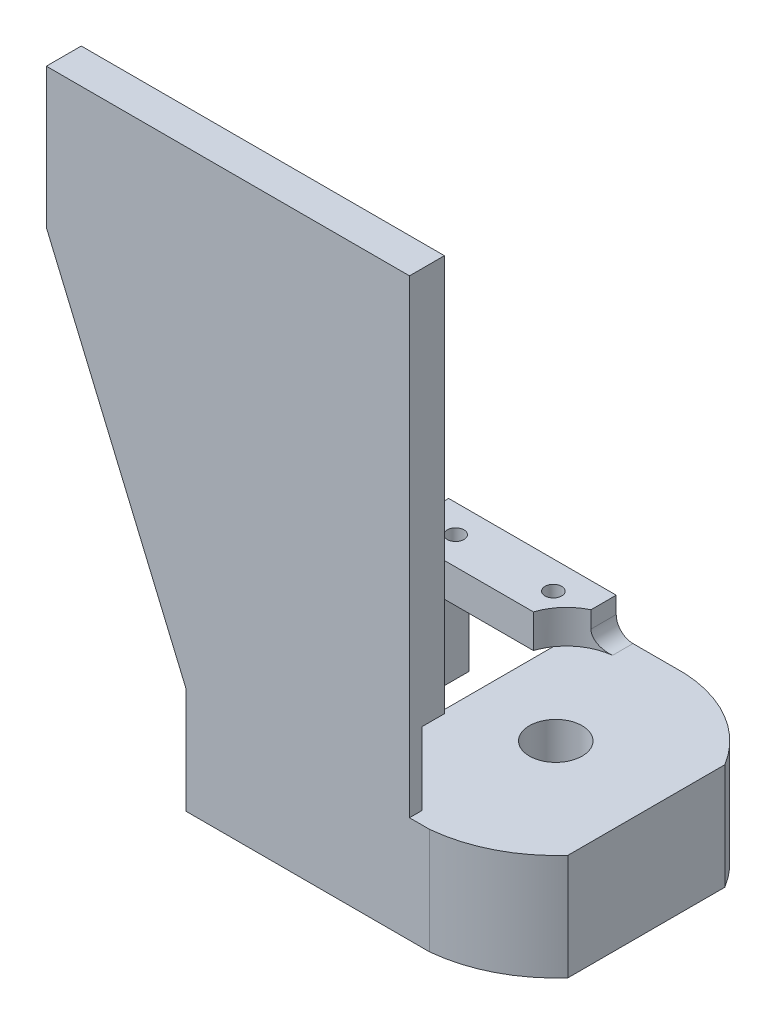
SolidWorks part; units mm, degrees
ref_plane "Front Plane" through (0, 0, 0) normal (0, 0, 1) x (1, 0, 0)
ref_plane "Top Plane" through (0, 0, 0) normal (0, 1, 0) x (1, 0, 0)
ref_plane "Right Plane" through (0, 0, 0) normal (1, 0, 0) x (0, 0, -1)
sketch "Sketch1" plane through (0, 0, 0) normal (0, 1, 0) x (1, 0, 0)
  line L0 (-5.7502, 0) -> (11.7498, 0) construction
  circle A0 centre (-5.7502, 0) radius 1.5 construction
  circle A1 centre (11.7498, 0) radius 1.5 construction
  dimension "D1" = 3
  dimension "D2" = 17.5
sketch "Sketch2" plane through (0, 0, 0) normal (0, 1, 0) x (1, 0, 0)
  line L0 (2.9998, -5) -> (2.9998, 5) construction
  line L1 (-12.0002, -5) -> (17.9998, -5)
  line L2 (-12.0002, -5) -> (-12.0002, 5)
  line L3 (-12.0002, 5) -> (17.9998, 5)
  line L4 (17.9998, -5) -> (17.9998, 5)
  line L5 (-5.7502, 0) -> (11.7498, 0) construction
  line L6 (-12.0002, 0) -> (17.9998, 0) construction
  point P6 (2.9998, 0)
  point P11 (2.9998, 0)
  dimension "D1" = 30
  dimension "D2" = 10
extrude "Boss-Extrude1" add sketch "Sketch2" along normal blind 25
sketch "Sketch3" plane through (0, 0, 5) normal (0, 0, 1) x (1, 0, 0)
  line L0 (2.9998, 25) -> (2.9998, 0) construction
  line L1 (-12.0002, 25) -> (17.9998, 25) construction
  line L2 (-5.7502, 0) -> (11.7498, 0) construction
  line L3 (-12.0002, 12.5) -> (17.9998, 12.5) construction
  line L4 (-12.0002, 25) -> (-12.0002, 0) construction
  line L5 (17.9998, 25) -> (17.9998, 0) construction
  line L6 (-12.0002, 0) -> (17.9998, 0) construction
  line L7 (-8.3502, 0) -> (14.3498, 0)
  line L8 (-8.3502, 0) -> (-8.3502, 19)
  line L9 (-8.3502, 19) -> (14.3498, 19)
  line L10 (14.3498, 0) -> (14.3498, 19)
  line L11 (-8.3502, 0) -> (14.3498, 19) construction
  line L12 (-8.3502, 19) -> (14.3498, 0) construction
  point P12 (2.9998, 12.5)
  dimension "D1" = 19
  dimension "D2" = 22.7
extrude "Cut-Extrude1" cut sketch "Sketch3" against normal through all
sketch "Sketch4" plane through (0, 0, 0) normal (0, -1, 0) x (1, 0, 0)
  circle A0 centre (-5.7502, 0) radius 1.5
  circle A1 centre (11.7498, 0) radius 1.5
extrude "Cut-Extrude2" cut sketch "Sketch4" against normal through all
sketch "Sketch5" plane through (0, 0, 5) normal (0, 0, 1) x (1, 0, 0)
  line L0 (13.2498, 0) -> (10.2498, 0) construction
  line L1 (17.9998, 19) -> (14.3498, 19)
  line L2 (17.9998, 19) -> (17.9998, 0)
  line L3 (17.9998, 0) -> (14.3498, 0)
  line L4 (14.3498, 19) -> (14.3498, 0)
  line L5 (14.3498, 0) -> (14.3498, 19) construction
  line L6 (14.3498, 19) -> (-8.3502, 19) construction
extrude "Boss-Extrude2" add sketch "Sketch5" along normal blind 37
sketch "Sketch6" plane through (0, 0, 5) normal (0, 0, 1) x (1, 0, 0)
  line L0 (-8.3502, 19) -> (-8.3502, 0) construction
  line L1 (-12.0002, 0) -> (-8.3502, 0)
  line L2 (-12.0002, 0) -> (-12.0002, 19)
  line L3 (-12.0002, 19) -> (-8.3502, 19)
  line L4 (-8.3502, 0) -> (-8.3502, 19)
  line L6 (14.3498, 19) -> (-8.3502, 19) construction
extrude "Boss-Extrude3" add sketch "Sketch6" along normal blind 37
sketch "Sketch11" plane through (14.3498, 0, 0) normal (-1, 0, 0) x (0, 0, 1)
  line L0 (42, 19) -> (5, 19) construction
  line L1 (42, 0) -> (32, 0)
  line L2 (42, 0) -> (42, 19)
  line L3 (42, 19) -> (32, 19)
  line L4 (32, 0) -> (32, 19)
  dimension "D1" = 10
extrude "Boss-Extrude7" add sketch "Sketch11" along normal up to surface (22.7 mm away) up to face at (-8.3502, 11.4, 15.8)
sketch "Sketch12" plane through (0, 0, 0) normal (0, -1, 0) x (1, 0, 0)
  line L0 (-8.3502, 32) -> (14.3498, 32) construction
  line L1 (0.3998, 32) -> (5.5998, 32)
  line L2 (0.3998, 32) -> (0.3998, 37.2)
  line L3 (0.3998, 37.2) -> (5.5998, 37.2)
  line L4 (5.5998, 32) -> (5.5998, 37.2)
  line L5 (0.3998, 34.6) -> (-8.3502, 34.6) construction
  line L6 (-8.3502, 34.6) -> (-8.3502, 32) construction
  line L7 (5.5998, 34.6) -> (14.3498, 34.6) construction
  line L8 (14.3498, 34.6) -> (14.3498, 32) construction
  dimension "D1" = 5.2
  dimension "D2" = 5.2
extrude "Cut-Extrude4" cut sketch "Sketch12" against normal blind 11.1
sketch "Sketch14" plane through (17.9998, 0, 0) normal (1, 0, 0) x (0, 0, -1)
  line L0 (-42, 19) -> (-5, 19) construction
  line L1 (-42, 0) -> (5, 0)
  line L2 (-42, 0) -> (-42, 19)
  line L3 (-42, 19) -> (5, 19)
  line L4 (5, 0) -> (5, 19)
  line L5 (5, 25) -> (5, 0) construction
extrude "Boss-Extrude8" add sketch "Sketch14" along normal blind 30
sketch "Sketch15" plane through (0, 19, 0) normal (0, 1, 0) x (1, 0, 0)
  line L0 (17.9998, 5) -> (17.9998, -42) construction
  line L1 (47.9998, -42) -> (-12.0002, -42) construction
  line L2 (17.9998, -17) -> (39.9998, -17) construction
  circle A0 centre (29.1798, -17) radius 4.72
  dimension "D1" = 9.44
  dimension "D2" = 11.18
  dimension "D3" = 25
extrude "Cut-Extrude6" cut sketch "Sketch15" against normal through all
sketch "Sketch16" plane through (0, 19, 0) normal (0, 1, 0) x (1, 0, 0)
  line L1 (-12.0002, -42) -> (27.9998, -42)
  line L2 (-12.0002, -42) -> (-12.0002, -35.75)
  line L5 (47.9998, -42) -> (-12.0002, -42) construction
  line L6 (29.1798, -21.72) -> (29.1798, -12.28) construction
  line L7 (24.4598, -17) -> (33.8998, -17) construction
  line L8 (-12.0002, -35.75) -> (27.9998, -35.75)
  line L9 (-8.3502, -32) -> (14.3498, -32) construction
  line L10 (27.9998, -42) -> (27.9998, -35.75)
  circle A1 centre (29.1798, -17) radius 4.72 construction
  point P1 (0, 0)
  point P18 (0, 0)
  point P20 (0, 0)
  dimension "D1" = 3.75
  dimension "D3" = 40
sketch "Sketch21" plane through (0, 19, 0) normal (0, 1, 0) x (1, 0, 0)
  line L0 (47.9998, 5) -> (17.9998, 5) construction
  line L1 (47.9998, 5) -> (47.9998, -42) construction
  line L2 (47.9998, -42) -> (-12.0002, -42) construction
  line L3 (30.3244, 5) -> (47.9998, 5)
  line L4 (47.9998, 5) -> (47.9998, -5.5493)
  line L5 (31.6062, -42) -> (47.9998, -42)
  line L6 (47.9998, -42) -> (47.9998, -33.6342)
  arc A0 (30.3244, 5) -> (47.9998, -5.5493) centre (29.1798, -17) cw
  arc A1 (47.9998, -33.6342) -> (31.6062, -42) centre (29.1798, -17) cw
  circle A2 centre (29.1798, -17) radius 4.72 construction
extrude "Cut-Extrude7" cut sketch "Sketch21" against normal through all
extrude "Boss-Extrude14" add sketch "Sketch16" along normal blind 84
sketch "Sketch23" plane through (0, 0, 42) normal (0, 0, 1) x (1, 0, 0)
  line L0 (-12.0002, 103) -> (-37.0002, 103)
  line L1 (-37.0002, 103) -> (-37.0002, 78)
  line L2 (-37.0002, 78) -> (-12.0002, 19)
  line L3 (-12.0002, 103) -> (-12.0002, 0) construction
  line L4 (31.6062, 19) -> (27.9998, 19) construction
  line L5 (-12.0002, 103) -> (-12.0002, 19)
  dimension "D1" = 25
  dimension "D2" = 25
extrude "Boss-Extrude15" add sketch "Sketch23" against normal up to surface (6.25 mm away) up to face at (7.9998, 61, 35.75)
sketch "Sketch24" plane through (0, 19, 0) normal (0, 1, 0) x (1, 0, 0)
  line L0 (7.3679, -23.4657) -> (29.1798, -17)
  line L1 (29.1798, -17) -> (41.9459, -35.8305)
  line L2 (-12.0002, -5) -> (17.9998, -5) construction
  line L3 (17.9998, -5) -> (17.9998, 5) construction
  line L4 (13.1769, -5) -> (17.9998, -5)
  line L5 (17.9998, -5) -> (17.9998, 0.4822)
  line L6 (17.9998, 5) -> (17.9998, -5) construction
  circle A0 centre (29.1798, -17) radius 22.75 construction
  arc A1 (7.3679, -23.4657) -> (41.9459, -35.8305) centre (29.1798, -17) ccw
  arc A3 (13.1769, -5) -> (17.9998, 0.4822) centre (22.0495, -7.943) cw
  point P12 (17.9998, 0.4822)
  dimension "D1" = 45.5
extrude "Cut-Extrude8" cut sketch "Sketch24" along normal blind 13
sketch "Sketch25" plane through (-12.0002, 0, 0) normal (-1, 0, 0) x (0, 0, 1)
  line L0 (5, 25) -> (35.75, 103)
  line L1 (35.75, 103) -> (35.75, 19)
  line L2 (35.75, 19) -> (5, 19)
  line L3 (5, 19) -> (5, 25)
extrude "Boss-Extrude16" add sketch "Sketch25" against normal up to surface (3.65 mm away) up to face at (-8.3502, 11.4, 11.8)
sketch "Sketch26" plane through (0, 0, 0) normal (0, -1, 0) x (1, 0, 0)
  line L0 (-10.1752, -5) -> (-10.1752, 20.8) construction
  line L1 (-8.3502, -5) -> (-12.0002, -5) construction
  line L2 (-12.0002, 23.525) -> (-8.3502, 23.525)
  line L3 (-12.0002, -5) -> (-12.0002, 42) construction
  line L4 (-8.3502, -5) -> (-8.3502, 32) construction
  line L5 (-8.3502, 23.525) -> (-8.3502, 18.075)
  line L6 (-8.3502, 18.075) -> (-12.0002, 18.075)
  line L7 (-12.0002, 18.075) -> (-12.0002, 23.525)
  line L8 (-10.1752, 23.525) -> (-10.1752, 18.075) construction
  point P14 (0, 0)
  point P15 (-10.1752, 20.8)
  dimension "D1" = 25.8
  dimension "D2" = 5.45
extrude "Cut-Extrude9" cut sketch "Sketch26" against normal blind 3
fillet "Fillet3" radius 2 2 edges at (-8.3502, 9.5, 32) (14.3498, 9.5, 32)
fillet "Fillet4" radius 3 4 edges at (3.9727, 19, 35.75) (17.9998, 19, -2.7411) (-12.0002, 61, 35.75) (-8.3502, 61, 35.75)
